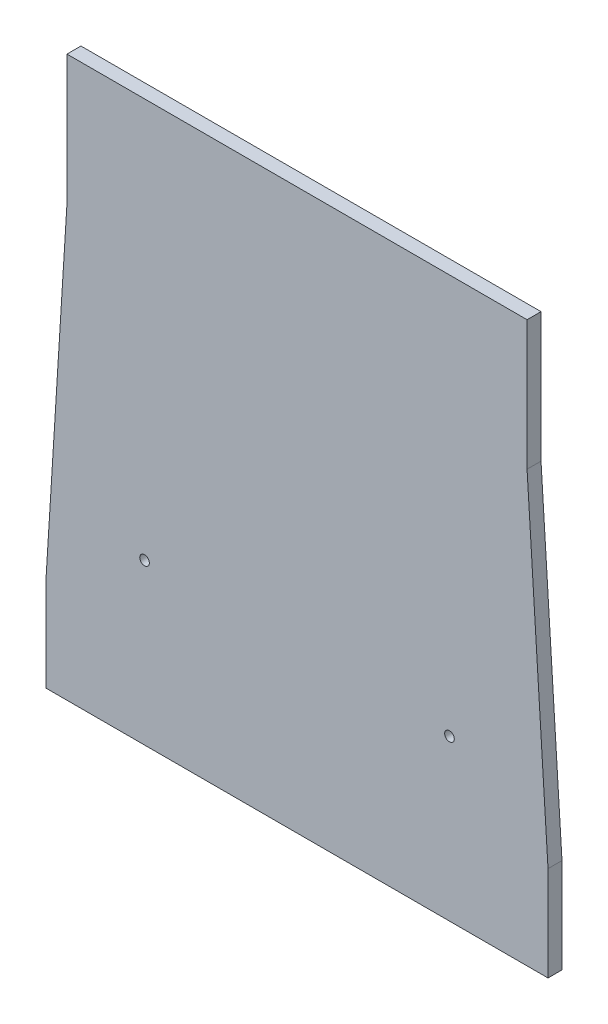
SolidWorks part; units mm, degrees
material "MDF"
ref_plane "Front Plane" through (0, 0, 0) normal (0, 0, 1) x (1, 0, 0)
ref_plane "Top Plane" through (0, 0, 0) normal (0, 1, 0) x (1, 0, 0)
ref_plane "Right Plane" through (0, 0, 0) normal (1, 0, 0) x (0, 0, -1)
sketch "Sketch1" plane through (0, 0, 0) normal (0, 0, 1) x (1, 0, 0)
  line L0 (0, -4273.1683) -> (0, -5592.0408) construction
  line L1 (209.0395, -5469.1795) -> (-209.0395, -5469.1795)
  line L2 (209.0395, -5469.1795) -> (209.0395, -5053.2545)
  line L3 (209.0395, -5053.2545) -> (-209.0395, -5053.2545)
  line L4 (0, -5469.1795) -> (0, -5053.2545) construction
  line L5 (-209.0395, -5469.1795) -> (-209.0395, -5053.2545)
  dimension "D1" = 209.0395
  dimension "D2" = 120.65
  dimension "D3" = 415.925
extrude "Boss-Extrude1" add sketch "Sketch1" along normal blind 12.7
sketch "Sketch2" plane through (0, 0, 0) normal (0, 0, -1) x (-1, 0, 0)
  line L1 (-209.0395, -5469.1795) -> (209.0395, -5469.1795)
  line L2 (-209.0395, -5469.1795) -> (-209.0395, -5548.8695)
  line L3 (-209.0395, -5548.8695) -> (209.0395, -5548.8695)
  line L4 (209.0395, -5469.1795) -> (209.0395, -5548.8695)
  line L8 (209.0395, -5053.2545) -> (209.0395, -5469.1795) construction
  dimension "D1" = 79.69
extrude "Boss-Extrude2" add sketch "Sketch2" against normal through all
sketch "Sketch3" plane through (0, 0, 0) normal (0, 0, -1) x (-1, 0, 0)
  line L1 (209.0395, -5024.8784) -> (-209.0395, -5024.8784)
  line L2 (209.0395, -5024.8784) -> (209.0395, -5053.2545)
  line L3 (209.0395, -5053.2545) -> (-209.0395, -5053.2545)
  line L4 (-209.0395, -5024.8784) -> (-209.0395, -5053.2545)
extrude "Boss-Extrude3" add sketch "Sketch3" against normal through all
sketch "Sketch4" plane through (0, 0, 0) normal (0, 0, -1) x (-1, 0, 0)
  line L0 (209.0388, -5447.3528) -> (228.0888, -5447.3528)
  line L1 (228.0888, -5447.3528) -> (228.0888, -5548.8695)
  line L2 (-209.0395, -5548.8695) -> (209.0395, -5548.8695) construction
  line L3 (228.0888, -5548.8695) -> (209.0395, -5548.8695)
  line L4 (209.0395, -5548.8695) -> (209.0388, -5447.3528)
  line L5 (0, -5562.8703) -> (0, -5024.8784) construction
  line L6 (209.0395, -5024.8784) -> (-209.0395, -5024.8784) construction
  line L7 (-209.0395, -5548.8695) -> (-209.0388, -5447.3528)
  line L8 (-228.0888, -5548.8695) -> (-209.0395, -5548.8695)
  line L9 (-228.0888, -5447.3528) -> (-228.0888, -5548.8695)
  line L10 (-209.0388, -5447.3528) -> (-228.0888, -5447.3528)
extrude "Boss-Extrude4" add sketch "Sketch4" against normal through all
chamfer "Chamfer1" distance 19.05 distance2 304.8 2 edges at (-209.0395, -5447.3528, 6.35) (209.0395, -5447.3528, 6.35) first distance on face at (-218.5641, -5447.3528, 6.35) first distance on face at (218.5641, -5447.3528, 6.35)
sketch "Sketch5" plane through (228.0888, 0, 0) normal (1, 0, 0) x (0, 0, -1)
  line L0 (0, -5447.3417) -> (0, -5548.8695) construction
  line L1 (-12.7, -5548.8695) -> (0, -5548.8695)
  line L2 (-12.7, -5548.8695) -> (-12.7, -5533.4155)
  line L3 (-12.7, -5533.4155) -> (0, -5533.4155)
  line L4 (0, -5548.8695) -> (0, -5533.4155)
extrude "Cut-Extrude1" cut sketch "Sketch5" against normal through all
hole_wizard "5/16 Clearance Hole1" positions "Sketch6" profile "Sketch7" hole size "5/16" standard "ANSI Inch" end condition through all
sketch "Sketch6" plane through (0, 0, 0) normal (0, 0, -1) x (-1, 0, 0)
  point P0 (138.551, -5387.9638)
  point P3 (-138.551, -5387.9638)
sketch "Sketch7" plane through (-138.551, -5387.9638, 0) normal (1, 0, 0) x (0, 1, 0)
  line L0 (0, 0) -> (0, 12.7)
  line L1 (0, 12.7) -> (4.365, 12.7)
  line L2 (4.365, 12.7) -> (4.365, 0)
  line L5 (4.365, 0) -> (0, 0)
  line L11 (0, -6.35) -> (0, 107.95) construction
  dimension "Thru Hole Dia." = 8.73
  dimension "Thru Hole Depth" = 12.7
